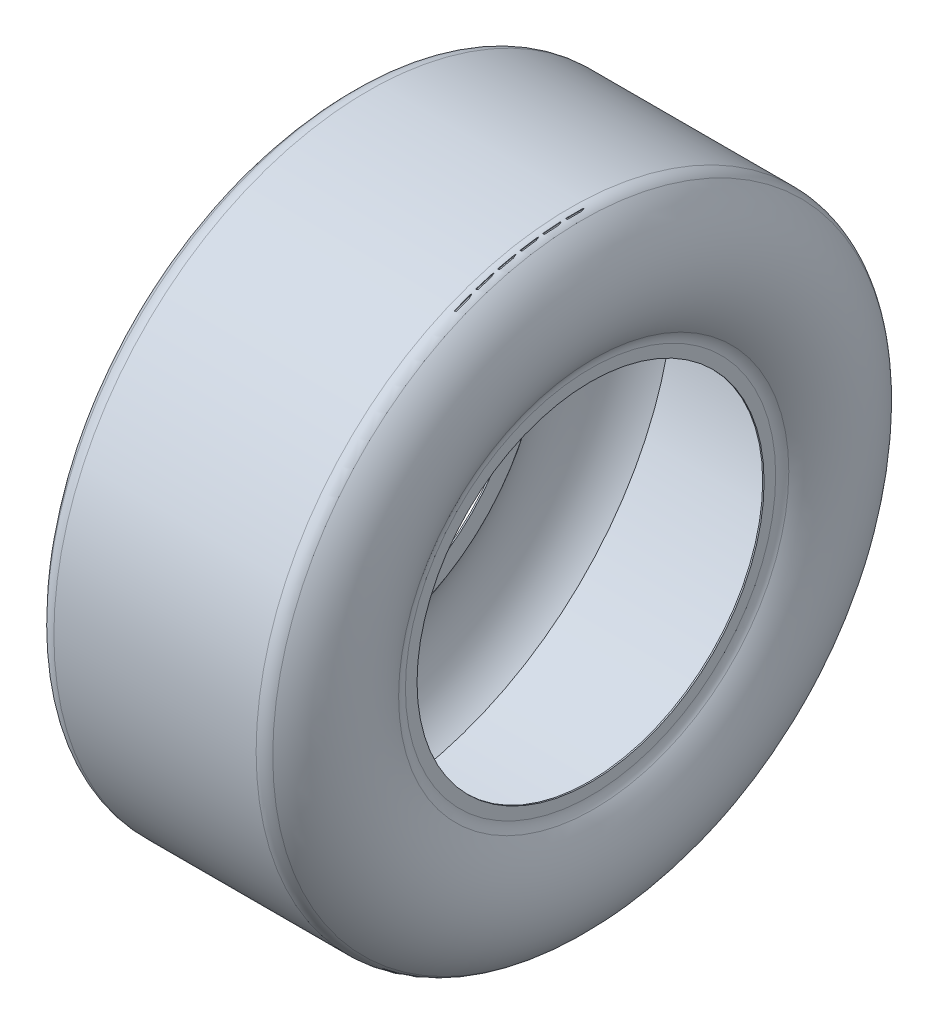
SolidWorks part; units mm, degrees
material "Silicon Rubber"
ref_plane "Front Plane" through (0, 0, 0) normal (0, 0, 1) x (1, 0, 0)
ref_plane "Top Plane" through (0, 0, 0) normal (0, 1, 0) x (1, 0, 0)
ref_plane "Right Plane" through (0, 0, 0) normal (1, 0, 0) x (0, 0, -1)
sketch "Sketch1" plane through (0, 0, 0) normal (0, 0, 1) x (1, 0, 0)
  line L0 (0, 0) -> (0, 229.87)
  line L1 (-88.9, 127) -> (0, 127)
  line L2 (0, 229.87) -> (-78.74, 229.87)
  line L3 (-102.87, 179.6939) -> (0, 179.6939)
  line L4 (0, 0) -> (-205.0641, 0)
  line L5 (-88.9, 139.7) -> (-88.9, 127)
  arc A0 (-88.9, 139.7) -> (-78.74, 229.87) centre (-38.6368, 179.6939) cw
  dimension "D1" = 229.87
  dimension "D2" = 88.9
  dimension "D3" = 127
  dimension "D4" = 78.74
  dimension "D5" = 102.87
  dimension "D6" = 12.7
revolve "Revolve1" add sketch "Sketch1" angle 360 about L4 region at (-48.2216, 154.1831, 0) region at (-48.0242, 203.7808, 0)
mirror "Mirror1" about plane through (0, 0, 0) normal (1, 0, 0) of "Revolve1"
shell "Shell1" thickness 1.016 removed face at (-88.9, 0, -127)
fillet "Fillet1" radius 12.7 4 edges at (-78.74, 0, -229.87) (78.74, 0, -229.87) (88.9, 0, -139.7) (-88.9, 0, -139.7)
